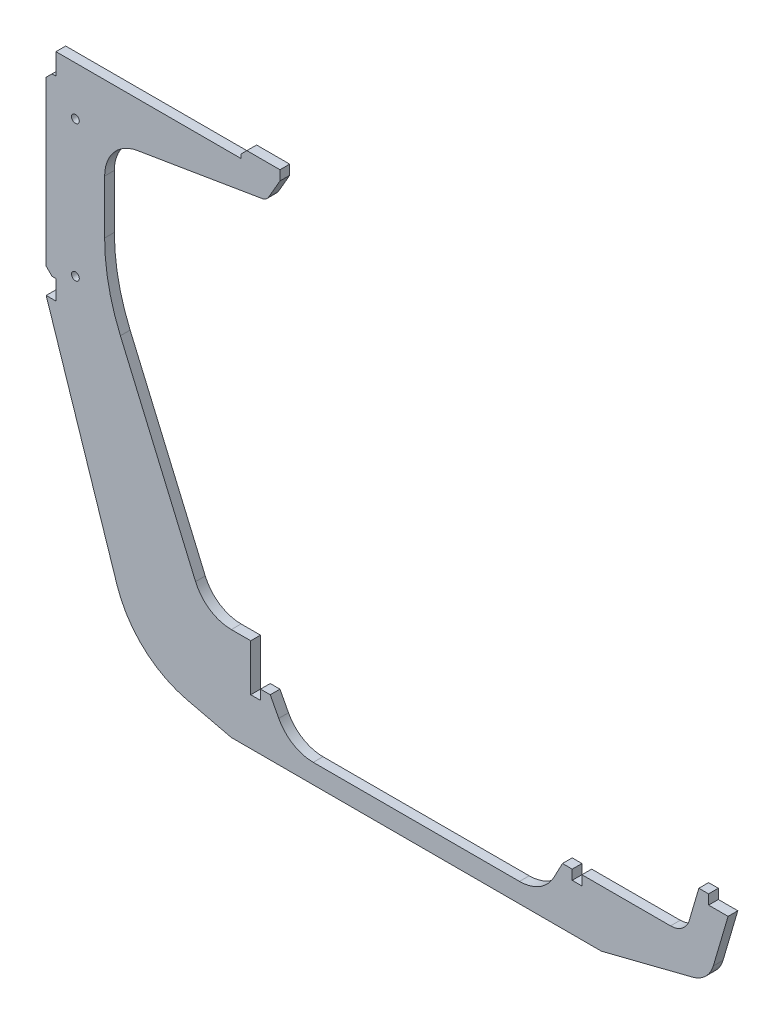
SolidWorks part; units mm, degrees
material "Stal węglowa"
ref_plane "Front" through (0, 0, 0) normal (0, 0, 1) x (1, 0, 0)
ref_plane "Top" through (0, 0, 0) normal (0, 1, 0) x (1, 0, 0)
ref_plane "Right" through (0, 0, 0) normal (1, 0, 0) x (0, 0, -1)
sketch "Szkic1" plane through (0, 0, 0) normal (0, 0, 1) x (1, 0, 0)
  line L39 (-65.2026, -126.4344) -> (124.7974, -126.4344)
  line L40 (124.7974, -126.4344) -> (171.4993, -114.6032)
  line L41 (114.7974, -97.4344) -> (160.2659, -97.4344)
  line L42 (109.7974, -97.4344) -> (109.7974, -102.4344)
  line L43 (109.7974, -102.4344) -> (114.7974, -102.4344)
  line L44 (114.7974, -102.4344) -> (114.7974, -97.4344)
  line L45 (109.7974, -97.4344) -> (104.7974, -97.4344)
  line L46 (100.4211, -105.7493) -> (104.7974, -97.4344)
  line L47 (-23.128, -116.4344) -> (82.7227, -116.4344)
  line L48 (-50.2026, -97.4344) -> (-50.2026, -102.4344)
  line L49 (-50.2026, -102.4344) -> (-55.2026, -102.4344)
  line L50 (-50.2026, -97.4344) -> (-45.2026, -97.4344)
  line L51 (-40.8263, -105.7493) -> (-45.2026, -97.4344)
  line L52 (-55.2026, -102.4344) -> (-55.2026, -78.4344)
  line L53 (-55.2026, -78.4344) -> (-65.1576, -78.4344)
  line L54 (-65.2026, -126.4344) -> (-87.8724, -121.0503)
  line L55 (-122.1171, 23.6994) -> (-83.5405, -66.3128)
  line L56 (-160.2026, 22.5656) -> (-123.814, -88.0305)
  line L57 (-160.2026, 119.5656) -> (-160.2026, 35.5656)
  line L58 (-130.2026, 90.6231) -> (-130.2026, 63.0914)
  line L59 (-49.4779, 121.0197) -> (-113.4906, 110.3509)
  line L60 (-40.2026, 138.4407) -> (-57.2026, 138.4407)
  line L61 (-60.2026, 135.4407) -> (-60.2026, 133.4407)
  line L62 (-155.2026, 122.5656) -> (-157.2026, 122.5656)
  line L63 (-160.2026, 22.5656) -> (-155.2026, 22.5656)
  line L64 (-155.2026, 32.5656) -> (-157.2026, 32.5656)
  line L65 (-155.2026, 133.4407) -> (-155.2026, 122.5656)
  line L66 (-155.2026, 22.5656) -> (-155.2026, 32.5656)
  line L67 (-40.2026, 138.4407) -> (-40.2026, 133.4407)
  line L68 (-60.2026, 133.4407) -> (-155.2026, 133.4407)
  line L69 (179.7974, -73.4344) -> (174.7974, -73.4344)
  line L70 (189.7974, -78.4344) -> (179.7974, -78.4344)
  line L71 (174.7974, -73.4344) -> (169.861, -90.251)
  line L72 (179.7974, -78.4344) -> (179.7974, -73.4344)
  line L73 (189.7974, -78.4344) -> (182.2084, -104.2874)
  line L74 (-157.2026, 32.5656) -> (-160.2026, 35.5656)
  line L75 (-157.2026, 122.5656) -> (-160.2026, 119.5656)
  line L76 (-57.2026, 138.4407) -> (-60.2026, 135.4407)
  line L77 (-40.2026, 133.4407) -> (-45.9698, 123.4517)
  arc A11 (82.7227, -116.4344) -> (100.4211, -105.7493) centre (82.7227, -96.4344) ccw
  arc A12 (-40.8263, -105.7493) -> (-23.128, -116.4344) centre (-23.128, -96.4344) ccw
  arc A13 (-123.814, -88.0305) -> (-87.8724, -121.0503) centre (-76.3188, -72.4035) ccw
  arc A14 (-130.2026, 63.0914) -> (-122.1171, 23.6994) centre (-30.2026, 63.0914) ccw
  arc A15 (-113.4906, 110.3509) -> (-130.2026, 90.6231) centre (-110.2026, 90.6231) ccw
  arc A16 (-83.5405, -66.3128) -> (-65.1576, -78.4344) centre (-65.1576, -58.4344) ccw
  arc A17 (171.4993, -114.6032) -> (182.2084, -104.2874) centre (167.8157, -100.0626) ccw
  arc A18 (160.2659, -97.4344) -> (169.861, -90.251) centre (160.2659, -87.4344) ccw
  circle A19 centre (-145.2026, 38.5656) radius 2
  circle A20 centre (-145.2026, 108.5656) radius 2
  arc A21 (-49.4779, 121.0197) -> (-45.9698, 123.4517) centre (-50.2999, 125.9517) ccw
extrude "Dodanie-wyciągnięcie1" add sketch "Szkic1" along normal blind 5
